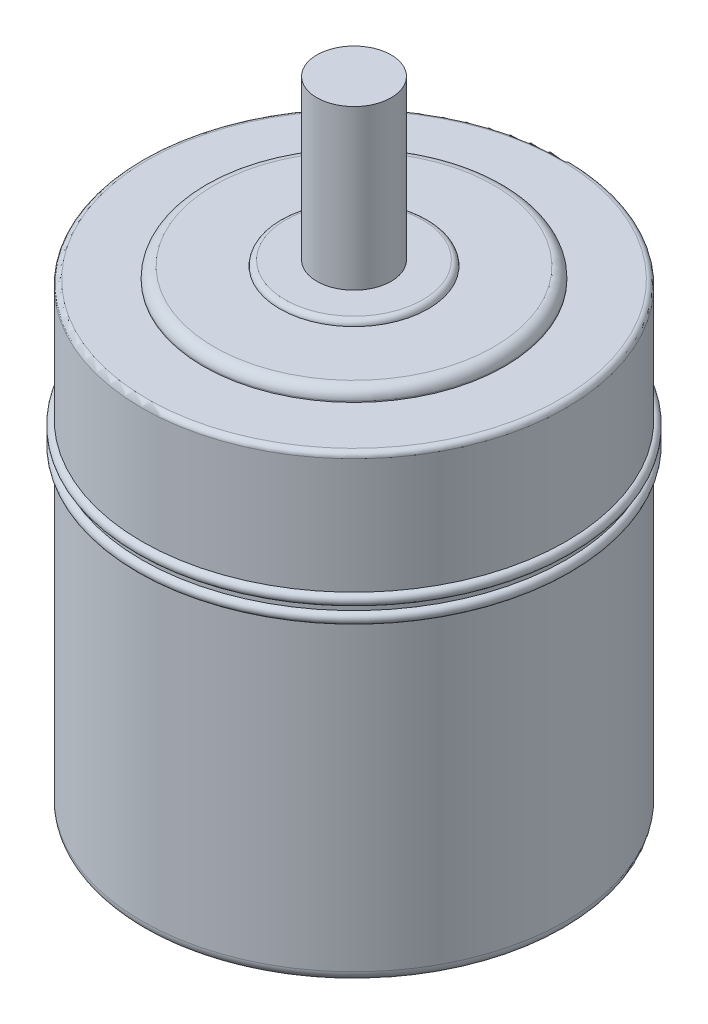
SolidWorks part; units mm, degrees
ref_plane "Front Plane" through (0, 0, 0) normal (0, 0, 1) x (1, 0, 0)
ref_plane "Top Plane" through (0, 0, 0) normal (0, 1, 0) x (1, 0, 0)
ref_plane "Right Plane" through (0, 0, 0) normal (1, 0, 0) x (0, 0, -1)
sketch "Sketch1" plane through (0, 0, 0) normal (0, 0, 1) x (1, 0, 0)
  line L0 (0, 0) -> (0, 76.2)
  line L1 (0, 76.2) -> (4.445, 76.2)
  line L2 (4.445, 76.2) -> (4.445, 57.15)
  line L4 (25.4, 55.118) -> (25.4, 0)
  line L5 (25.4, 0) -> (0, 0)
  line L6 (4.445, 57.15) -> (8.89, 57.15)
  line L7 (8.89, 57.15) -> (8.89, 56.515)
  line L8 (8.89, 56.515) -> (18.034, 56.515)
  line L9 (18.034, 56.515) -> (18.034, 55.118)
  line L10 (18.034, 55.118) -> (25.4, 55.118)
  dimension "D1" = 25.4
  dimension "D2" = 76.2
  dimension "D3" = 4.445
  dimension "D4" = 8.89
  dimension "D5" = 0.635
  dimension "D6" = 1.397
  dimension "D7" = 57.15
  dimension "D8" = 18.034
revolve "Revolve1" add sketch "Sketch1" angle 360 about L0
sketch "Sketch2" plane through (0, 0, 0) normal (0, 0, 1) x (1, 0, 0)
  line L1 (25.4, 0) -> (25.4, 55.118) construction
  line L2 (0, 0) -> (0, 23.6538) construction
  circle A2 centre (25.4, 40.005) radius 0.635
  circle A3 centre (25.4, 38.1) radius 0.635
  dimension "D1" = 1.27
  dimension "D2" = 1.905
  dimension "D3" = 38.1
revolve "Revolve2" add sketch "Sketch2" angle 360 about L2
fillet "Fillet1" radius 0.635 1 edges at (8.89, 57.15, 0)
fillet "Fillet2" radius 1.27 2 edges at (18.034, 56.515, 0) (25.4, 0, 0)
fillet "Fillet3" radius 0.635 1 edges at (25.4, 55.118, 0)
